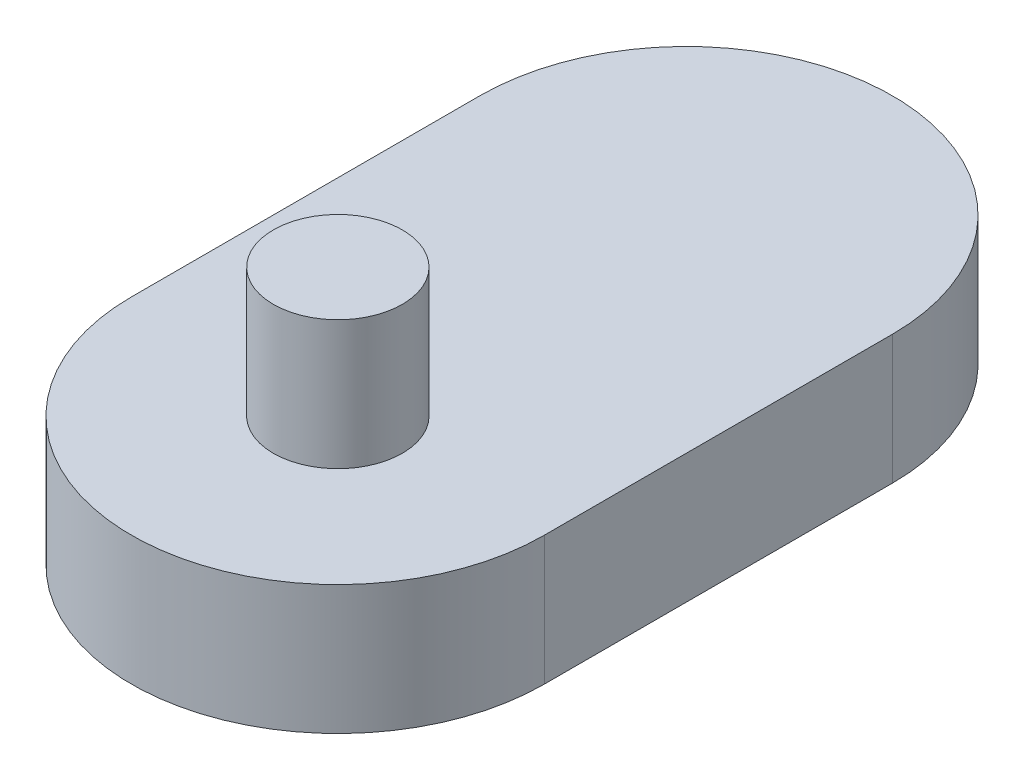
SolidWorks part; units mm, degrees
ref_plane "Front Plane" through (0, 0, 0) normal (0, 0, 1) x (1, 0, 0)
ref_plane "Top Plane" through (0, 0, 0) normal (0, 1, 0) x (1, 0, 0)
ref_plane "Right Plane" through (0, 0, 0) normal (1, 0, 0) x (0, 0, -1)
sketch "Sketch1" plane through (0, 0, 0) normal (0, 1, 0) x (1, 0, 0)
  line L0 (0, 9) -> (0, -9) construction
  line L1 (0, 6.75) -> (0, 0) construction
  line L2 (4, 6.75) -> (4, 0)
  line L3 (-4, 6.75) -> (-4, 0)
  arc A3 (4, 6.75) -> (-4, 6.75) centre (0, 6.75) ccw
  arc A4 (-4, 0) -> (4, 0) centre (0, 0) ccw
  point P1 (0, 3.375)
  dimension "D1" = 4
  dimension "D2" = 6.75
extrude "Boss-Extrude1" add sketch "Sketch1" along normal blind 2.5 contours L3 A4 L2 A3
extrude "Boss-Extrude2" add sketch "Sketch1<3>" along direction (0, 1, 0) on the side of the normal blind 2.5
sketch "Sketch1<3>" plane through (0, 0, 0) normal (0, 1, 0) x (1, 0, 0) same geometry as "Sketch1"
sketch "Sketch3" plane through (0, 2.5, 0) normal (0, 1, 0) x (1, 0, 0)
  circle A2 centre (0, 0) radius 1.25
  point P8 (1.9671, 1.7346)
  dimension "D1" = 2.5
extrude "Boss-Extrude3" add sketch "Sketch3" along normal blind 2.5
sketch "Sketch4" plane through (0, 0, 0) normal (0, -1, 0) x (1, 0, 0)
  circle A0 centre (0, -6.75) radius 1.25
  arc A1 (-4, -6.75) -> (4, -6.75) centre (0, -6.75) ccw construction
  dimension "D1" = 2.5
extrude "Boss-Extrude4" add sketch "Sketch4" along normal blind 2.5
